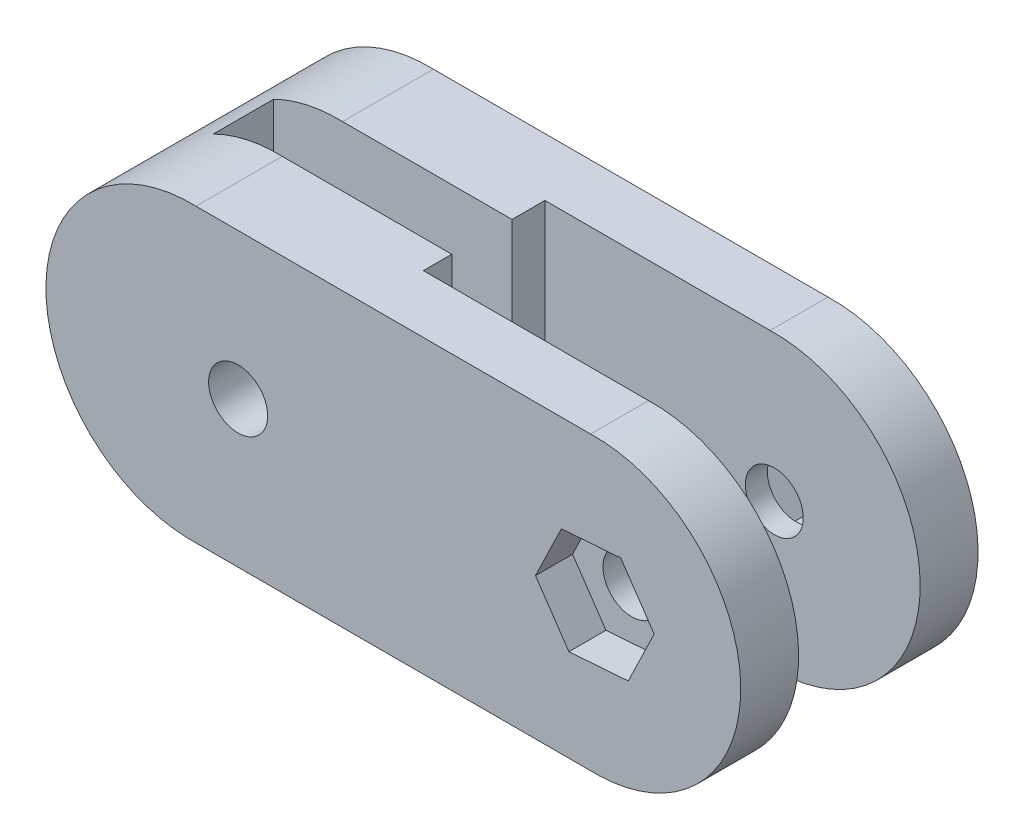
SolidWorks part; units mm, degrees
ref_plane "Front" through (0, 0, 0) normal (0, 0, 1) x (1, 0, 0)
ref_plane "Top" through (0, 0, 0) normal (0, 1, 0) x (1, 0, 0)
ref_plane "Right" through (0, 0, 0) normal (1, 0, 0) x (0, 0, -1)
sketch "Sketch1" plane through (0, 0, 0) normal (0, 0, 1) x (1, 0, 0)
  line L0 (0.4595, 15.9954) -> (9.4046, 15.9954)
  line L1 (9.4046, 15.9954) -> (9.4046, -15.9954)
  line L2 (9.4046, -15.9954) -> (-0.4595, -15.9954)
  arc A1 (0.4595, 15.9954) -> (-0.4595, -15.9954) centre (0, 0) ccw
  circle A2 centre (5.08, 0) radius 3.2381
  dimension "D1" = 6.4762
  dimension "D2" = 16.002
  dimension "D3" = 8.9451
  dimension "D4" = 5.08
extrude "Boss-Extrude1" add sketch "Sketch1" along normal blind 3.175 and the other way blind 3.175
sketch "Sketch3" plane through (0, 0, 3.175) normal (0, 0, 1) x (1, 0, 0)
  line L1 (9.4046, 15.9954) -> (0.4595, 15.9954) construction
  line L3 (9.4046, 15.9954) -> (0.4595, 15.9954)
  line L4 (22.1046, 30.8623) -> (22.1046, 5.0768) construction
  line L5 (9.4046, 15.9954) -> (9.4046, -15.9954) construction
  line L6 (9.4046, 15.9954) -> (43.7497, 15.9954)
  line L7 (9.4046, -15.9954) -> (44.6687, -15.9954)
  line L8 (9.4046, 15.9954) -> (9.4046, -15.9954)
  line L9 (-0.4595, -15.9954) -> (9.4046, -15.9954) construction
  line L10 (-0.4595, -15.9954) -> (9.4046, -15.9954)
  circle A0 centre (5.08, 0) radius 3.2381
  arc A1 (0.4595, 15.9954) -> (-0.4595, -15.9954) centre (0, 0) ccw construction
  arc A3 (0.4595, 15.9954) -> (-0.4595, -15.9954) centre (0, 0) ccw
  circle A4 centre (44.2092, 0) radius 3.175
  arc A5 (43.7497, 15.9954) -> (44.6687, -15.9954) centre (44.2092, 0) cw
  dimension "D1" = 12.7
  dimension "D2" = 9.8641
extrude "Boss-Extrude3" add sketch "Sketch3" against normal blind 6.35 contours A5 L6 L7 A4 region at (32.9931, 0, 3.175)
sketch "Sketch4" plane through (0, 0, 3.175) normal (0, 0, 1) x (1, 0, 0)
  line L6 (19.05, 15.9954) -> (19.05, -15.9954)
  line L7 (19.05, 15.9954) -> (0.4595, 15.9954)
  line L8 (-0.4595, -15.9954) -> (19.05, -15.9954)
  arc A4 (0.4595, 15.9954) -> (-0.4595, -15.9954) centre (0, 0) ccw construction
  arc A5 (0.4595, 15.9954) -> (-0.4595, -15.9954) centre (0, 0) ccw
  circle A7 centre (5.08, 0) radius 3.2381 construction
  circle A10 centre (5.08, 0) radius 3.2381
  dimension "D1" = 19.05
extrude "Boss-Extrude4" add sketch "Sketch4" along normal blind 13.335
sketch "Sketch6" plane through (0, 0, 16.51) normal (0, 0, 1) x (1, 0, 0)
  line L0 (43.7497, 15.9954) -> (19.05, 15.9954) construction
  line L1 (19.05, -15.9954) -> (44.6687, -15.9954) construction
  line L2 (-0.4595, -15.9954) -> (19.05, -15.9954) construction
  line L3 (19.05, -15.9954) -> (44.6687, -15.9954)
  line L4 (-0.4595, -15.9954) -> (19.05, -15.9954)
  line L5 (19.05, 15.9954) -> (0.4595, 15.9954) construction
  line L6 (43.7497, 15.9954) -> (19.05, 15.9954)
  line L7 (19.05, 15.9954) -> (0.4595, 15.9954)
  arc A0 (44.6687, -15.9954) -> (43.7497, 15.9954) centre (44.2092, 0) ccw construction
  circle A1 centre (44.2092, 0) radius 3.175 construction
  arc A3 (0.4595, 15.9954) -> (-0.4595, -15.9954) centre (0, 0) ccw construction
  arc A4 (44.6687, -15.9954) -> (43.7497, 15.9954) centre (44.2092, 0) ccw
  circle A5 centre (44.2092, 0) radius 3.175
  arc A7 (0.4595, 15.9954) -> (-0.4595, -15.9954) centre (0, 0) ccw
  circle A9 centre (5.08, 0) radius 3.2381 construction
  circle A10 centre (5.08, 0) radius 3.2381
  arc M1 (0.4595, 15.9954) -> (-0.4595, -15.9954) centre (0, 0) ccw
  line M2 (-0.4595, -15.9954) -> (19.05, -15.9954)
  line M3 (19.05, -15.9954) -> (19.05, 15.9954)
  line M4 (19.05, 15.9954) -> (0.4595, 15.9954)
extrude "Boss-Extrude6" add sketch "Sketch6" along normal blind 6.35 contours M4 M1 M2 M3 | L3 A4 A5 M4 M3 region at (37.9194, 0.0001, 16.51) region at (9.2953, -15.5208, 16.51)
sketch "Sketch7" plane through (0, 0, 22.86) normal (0, 0, 1) x (1, 0, 0)
  line L1 (50.7177, 0.4743) -> (47.0527, 5.8737)
  line L2 (47.0527, 5.8737) -> (40.5442, 5.3994)
  line L3 (40.5442, 5.3994) -> (37.7007, -0.4743)
  line L4 (37.7007, -0.4743) -> (41.3657, -5.8737)
  line L5 (41.3657, -5.8737) -> (47.8742, -5.3994)
  line L6 (47.8742, -5.3994) -> (50.7177, 0.4743)
  circle A0 centre (44.2092, 0) radius 5.6515 construction
  point P0 (44.2092, 0)
  dimension "D1" = 11.303
extrude "Cut-Extrude1" cut sketch "Sketch7" against normal blind 4.064 and the other way through all
ref_plane "Plane7" through (0, 0, 9.779) normal (0, 0, 1) x (1, 0, 0)
mirror "Mirror3" about plane through (0, 0, 9.779) normal (0, 0, 1) of "Cut-Extrude1"
sketch "Sketch10" plane through (19.05, 0, 0) normal (1, 0, 0) x (0, 0, -1)
  line L5 (-13.3961, 24.5464) -> (-6.7844, 24.5464)
  line L6 (-10.0903, -15.9954) -> (-10.0903, -17.8123) construction
  line L7 (-32.4473, 0) -> (-36.8893, 0) construction
  line L8 (-13.3961, 24.5464) -> (-13.3961, -24.5464)
  line L9 (-13.3961, -24.5464) -> (-6.7844, -24.5464)
  line L10 (-6.7844, 24.5464) -> (-6.7844, -24.5464)
extrude "Cut-Extrude2" cut sketch "Sketch10" against normal blind 26.162
sketch "Sketch12" plane through (0, 0, 13.3961) normal (0, 0, -1) x (-1, 0, 0)
  line L0 (-19.05, 15.9954) -> (-19.05, -15.9954) construction
  line L1 (-19.05, 15.9954) -> (-19.05, -15.9954)
  circle A3 centre (-5.08, 0) radius 3.2381 construction
  point P0 (-5.08, 3.2381)
